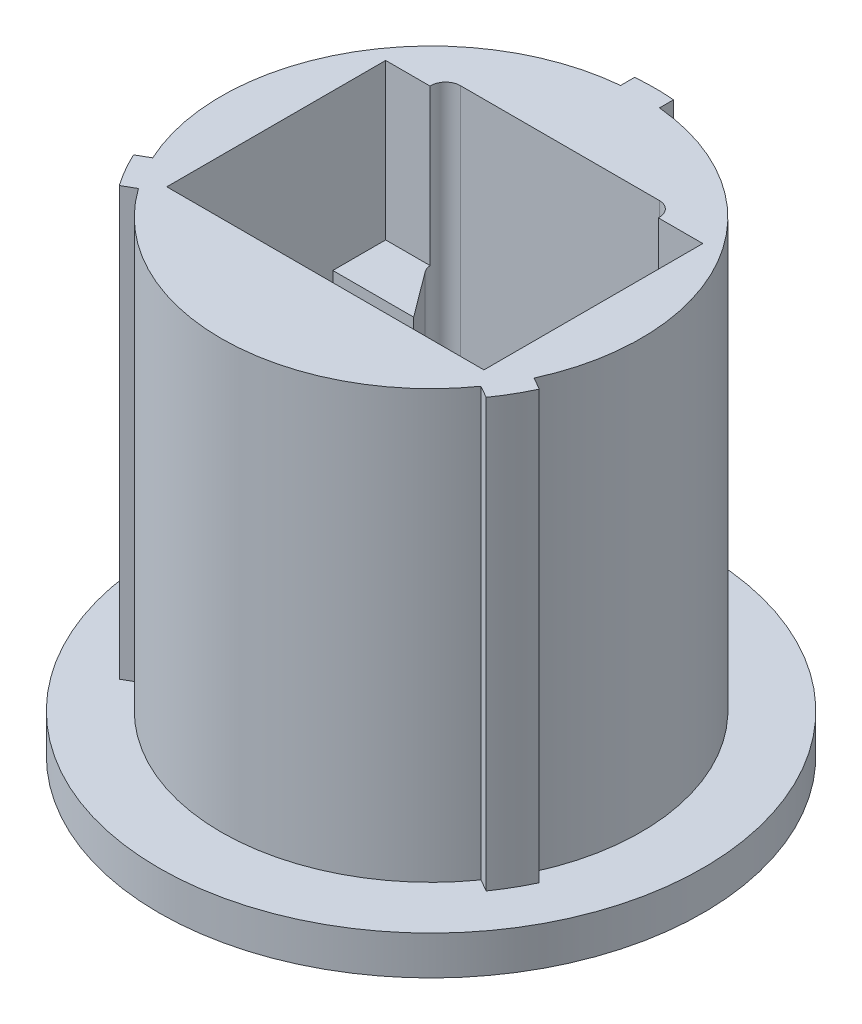
SolidWorks part; units mm, degrees
ref_plane "Front Plane" through (0, 0, 0) normal (0, 0, 1) x (1, 0, 0)
ref_plane "Top Plane" through (0, 0, 0) normal (0, 1, 0) x (1, 0, 0)
ref_plane "Right Plane" through (0, 0, 0) normal (1, 0, 0) x (0, 0, -1)
sketch "Sketch1" plane through (0, 0, 0) normal (0, 1, 0) x (1, 0, 0)
  line L0 (-0.7938, 9.1095) -> (-0.7938, 8.5357)
  line L1 (0.7937, 9.1095) -> (0.7937, 8.5357)
  line L2 (8.2859, -3.8673) -> (7.789, -3.5804)
  line L3 (7.4922, -5.2421) -> (6.9952, -4.9552)
  line L4 (-7.4922, -5.2421) -> (-6.9952, -4.9552)
  line L5 (-8.2859, -3.8673) -> (-7.789, -3.5804)
  arc A0 (-6.9952, -4.9552) -> (6.9952, -4.9552) centre (0, 0) ccw
  arc A1 (-8.2859, -3.8673) -> (-7.4922, -5.2421) centre (0, 0) ccw
  arc A2 (0.7937, 9.1095) -> (-0.7938, 9.1095) centre (0, 0) ccw
  arc A3 (7.4922, -5.2421) -> (8.2859, -3.8673) centre (0, 0) ccw
  arc A4 (7.789, -3.5804) -> (0.7937, 8.5357) centre (0, 0) ccw
  arc A5 (-0.7938, 8.5357) -> (-7.789, -3.5804) centre (0, 0) ccw
  point P18 (0, 0)
  dimension "D1" = 17.145
  dimension "D2" = 18.288
  dimension "D3" = 1.5875
  dimension "D4" = 3
extrude "Boss-Extrude1" add sketch "Sketch1" along normal blind 19.05
sketch "Sketch2" plane through (0, 19.05, 0) normal (0, 1, 0) x (1, 0, 0)
  line L0 (-3.175, 2.4638) -> (-4.5436, 4.3031)
  line L1 (-6.477, 2.4638) -> (6.477, 2.4638)
  line L2 (-6.477, 2.4638) -> (-6.477, 0.762)
  line L3 (-6.477, 0.762) -> (6.477, 0.762)
  line L4 (6.477, 2.4638) -> (6.477, 0.762)
  line L5 (-4.064, 5.2578) -> (4.064, 5.2578)
  line L6 (4.5436, 4.3031) -> (3.175, 2.4638)
  line L7 (3.175, 2.4638) -> (-3.175, 2.4638)
  arc A0 (-4.5436, 4.3031) -> (-4.064, 5.2578) centre (-4.064, 4.66) cw
  arc A1 (4.064, 5.2578) -> (4.5436, 4.3031) centre (4.064, 4.66) cw
  point P12 (0, 5.2578)
  point P13 (0, 2.4638)
  dimension "D1" = 1.7018
  dimension "D2" = 12.954
  dimension "D3" = 8.128
  dimension "D4" = 6.35
  dimension "D5" = 2.794
  dimension "D6" = 0.762
extrude "Cut-Extrude1" cut sketch "Sketch2" against normal through all contours A1 L5 A0 L0 L1 L6 region at (0, 19.05, -3.9469)
extrude "Cut-Extrude2" cut sketch "Sketch2<4>" against normal blind 18.2562 contours L4 L1 L2 L3 region at (0, 19.05, -1.6129)
sketch "Sketch2<4>" plane through (0, 19.05, 0) normal (0, 1, 0) x (1, 0, 0) same geometry as "Sketch2"
sketch "Sketch6" plane through (0, 0, 0) normal (1, 0, 0) x (0, 0, -1)
  line L0 (8.5357, 1.5875) -> (9.144, 1.5875)
  line L1 (8.5357, 1.5875) -> (8.5357, 0)
  line L3 (8.5357, 0) -> (9.144, 0)
  line L5 (9.144, 0) -> (9.144, 1.5875)
  line L6 (0, 19.7302) -> (0, -0.9338) construction
  dimension "D1" = 1.5875
revolve "Cut-Revolve2" cut sketch "Sketch6" angle 360 about L6
sketch "Sketch8" plane through (0, 0, 0) normal (1, 0, 0) x (0, 0, -1)
  line L1 (8.5357, 1.5875) -> (11.1125, 1.5875)
  line L2 (8.5357, 1.5875) -> (8.5357, 0)
  line L3 (8.5357, 0) -> (11.1125, 0)
  line L4 (11.1125, 1.5875) -> (11.1125, 0)
  line L8 (0, 4.4839) -> (0, -1.895) construction
  dimension "D1" = 11.1125
revolve "Revolve2" add sketch "Sketch8" angle 360 about L8
sketch "Sketch9" plane through (0, 19.05, 0) normal (0, 1, 0) x (1, 0, 0)
  line L1 (-6.477, 0.762) -> (6.477, 0.762)
  line L2 (-6.477, 0.762) -> (-6.477, -4.318)
  line L3 (-6.477, -4.318) -> (6.477, -4.318)
  line L4 (6.477, 0.762) -> (6.477, -4.318)
  line L5 (-6.477, 2.4638) -> (6.477, 2.4638)
  line L6 (-6.477, 2.4638) -> (-6.477, 4.6228)
  line L7 (-6.477, 4.6228) -> (6.477, 4.6228)
  line L8 (6.477, 2.4638) -> (6.477, 4.6228)
  dimension "D1" = 5.08
  dimension "D2" = 2.159
extrude "Cut-Extrude3" cut sketch "Sketch9" against normal blind 6.35
sketch "Sketch10" plane through (0, 0, -0.762) normal (0, 0, -1) x (-1, 0, 0)
  line L0 (-6.477, 0.7938) -> (-6.477, 12.7) construction
  line L1 (6.477, 0.7938) -> (-6.477, 0.7938) construction
  line L2 (6.477, 0.7938) -> (6.477, 12.7) construction
  circle A0 centre (-4.572, 7.3978) radius 1.016
  circle A1 centre (4.445, 7.3978) radius 1.016
  point P4 (-6.477, 6.7469)
  dimension "D1" = 1.905
  dimension "D3" = 2.032
  dimension "D2" = 6.604
  dimension "D4" = 2.032
sketch "Sketch11" plane through (0, 0, 0) normal (1, 0, 0) x (0, 0, -1)
  line L1 (5.969, 10.3188) -> (9.144, 10.3188)
  line L2 (5.969, 10.3188) -> (5.969, 5.2388)
  line L3 (5.969, 5.2388) -> (9.144, 5.2388)
  line L4 (9.144, 10.3188) -> (9.144, 5.2388)
  line L5 (2.4638, 0.7938) -> (0.762, 0.7938) construction
  line L6 (9.144, 1.5875) -> (9.144, 19.05) construction
  dimension "D1" = 3.175
  dimension "D2" = 5.08
  dimension "D3" = 4.445
extrude "Cut-Extrude5" cut sketch "Sketch11" against normal through all both and the other way through all
extrude "Cut-Extrude6" cut sketch "Sketch10" along normal through all
